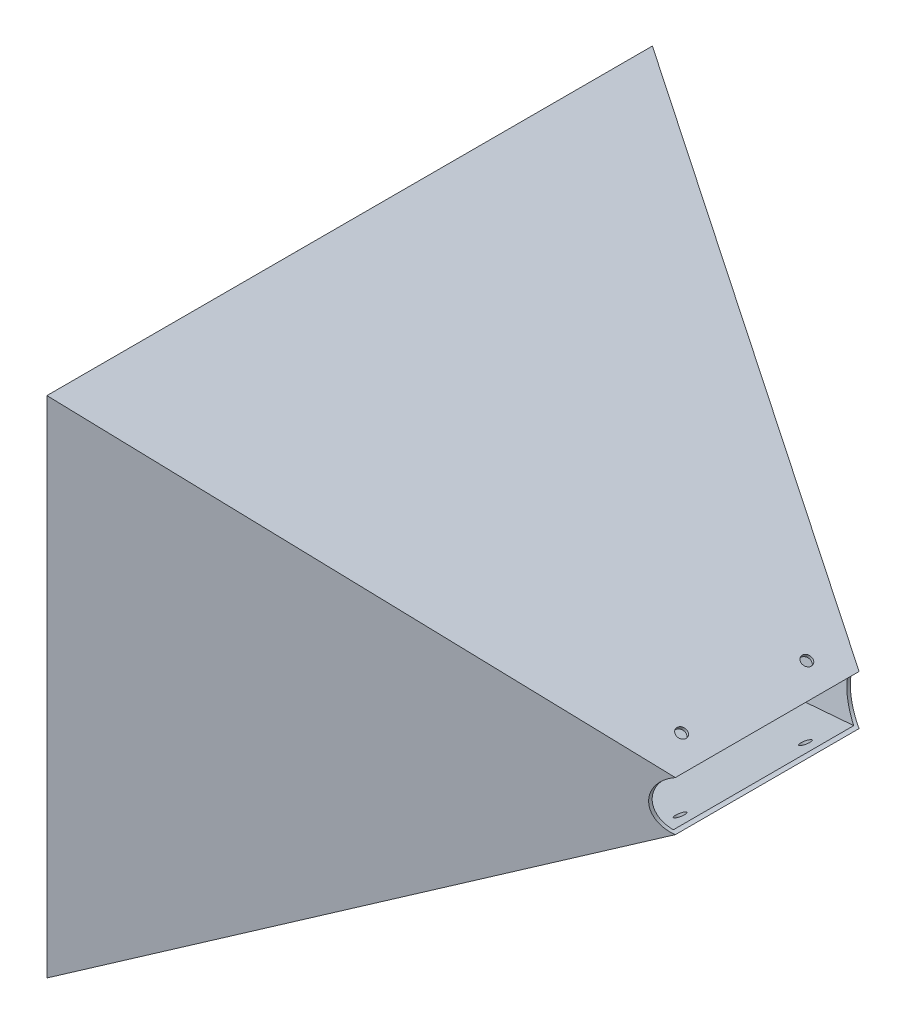
SolidWorks part; units mm, degrees
ref_plane "Front Plane" through (0, 0, 0) normal (0, 0, 1) x (1, 0, 0)
ref_plane "Top Plane" through (0, 0, 0) normal (0, 1, 0) x (1, 0, 0)
ref_plane "Right Plane" through (0, 0, 0) normal (1, 0, 0) x (0, 0, -1)
sketch "Sketch1" plane through (0, 0, 0) normal (0, 0, 1) x (1, 0, 0)
  line L0 (-4, -11.8427) -> (-204, -120.7957)
  line L1 (-4, -8.6168) -> (-204, -8.6168) construction
  line L2 (-204, 120.7957) -> (-4, 11.8427)
  line L3 (-4, -11.8427) -> (-4, -8.6168)
  line L4 (-4, 8.6168) -> (-4, 11.8427)
  line L5 (-204, -120.7957) -> (-204, 120.7957)
  arc A0 (-4, 8.6168) -> (-4, -8.6168) centre (0, 0) ccw
  dimension "D1" = 9.5
  dimension "D2" = 200
extrude "Boss-Extrude1" add sketch "Sketch1" along normal blind 290
ref_plane "Plane1" through (0, 0, 0) normal (0, -1, 0) x (-1, 0, 0)
sketch "Sketch2" plane through (0, 0, 0) normal (0, -1, 0) x (-1, 0, 0)
  line L0 (204, -145) -> (4, -145) construction
  line L1 (204, -290) -> (204, 0) construction
  line L2 (4, -290) -> (4, 0) construction
  line L3 (4, -145) -> (4, -189) construction
  line L4 (4, -189) -> (4, -101) construction
  line L5 (4, -145) -> (4, -101) construction
  line L6 (4, -189) -> (204, -290)
  line L7 (204, -290) -> (4, -290)
  line L8 (4, -290) -> (4, -189)
  line L9 (4, -101) -> (204, 0)
  line L10 (204, 0) -> (4, 0)
  line L11 (4, 0) -> (4, -101)
  dimension "D1" = 44
  dimension "D2" = 44
extrude "Cut-Extrude1" cut sketch "Sketch2" against normal blind 290 and the other way blind 290
shell "Shell3" thickness 1.5 removed face at (-6.75, 0, 145) removed face at (-204, 0, 145)
ref_plane "Plane2" through (4.0596, -7.4521, 0) normal (0.4784, -0.8782, 0) x (-0.8782, -0.4784, 0)
sketch "Sketch3" plane through (4.0596, -7.4521, 0) normal (0.4784, -0.8782, 0) x (-0.8782, -0.4784, 0)
  line L0 (9.178, -145) -> (236.9295, -145) construction
  line L1 (9.178, -189) -> (9.178, -101) construction
  line L2 (236.9295, -290) -> (236.9295, 0) construction
  line L3 (9.178, -145) -> (9.178, -175) construction
  line L4 (9.178, -175) -> (9.178, -115) construction
  line L5 (9.178, -145) -> (18.178, -145) construction
  line L6 (9.178, -175) -> (21.728, -175) construction
  line L7 (21.728, -175) -> (21.728, -115) construction
  line L8 (21.728, -115) -> (9.178, -115) construction
  circle A0 centre (21.728, -175) radius 2.5
  circle A1 centre (21.728, -115) radius 2.5
  dimension "D5" = 5
  dimension "D6" = 5
  dimension "D1" = 30
  dimension "D2" = 30
  dimension "D3" = 9
  dimension "D4" = 12.55
ref_plane "Plane3" through (4.0596, 7.4521, 0) normal (0.4784, 0.8782, 0) x (0.8782, -0.4784, 0)
sketch "Sketch4" plane through (4.0596, 7.4521, 0) normal (0.4784, 0.8782, 0) x (0.8782, -0.4784, 0)
  line L0 (-9.178, -101) -> (-9.178, -189) construction
  line L1 (-9.178, -189) -> (-9.178, -145) construction
  line L2 (-9.178, -145) -> (-236.9295, -145) construction
  line L3 (-236.9295, -290) -> (-236.9295, 0) construction
  line L4 (-9.178, -145) -> (-9.178, -115) construction
  line L5 (-9.178, -115) -> (-9.178, -175) construction
  line L6 (-9.178, -115) -> (-21.728, -115) construction
  line L7 (-21.728, -115) -> (-21.728, -175) construction
  line L8 (-21.728, -175) -> (-9.178, -175) construction
  circle A0 centre (-21.728, -115) radius 2.5
  circle A1 centre (-21.728, -175) radius 2.5
  dimension "D4" = 5
  dimension "D5" = 5
  dimension "D1" = 30
  dimension "D2" = 30
  dimension "D3" = 12.55
extrude "Cut-Extrude2" cut sketch "Sketch3" against normal blind 20
extrude "Cut-Extrude3" cut sketch "Sketch4" against normal blind 18 contours A1 | A0
ref_plane "Plane4" through (0, 0, 145) normal (0, 0, 1) x (1, 0, 0)
sketch "Sketch6" plane through (0, 0, 145) normal (0, 0, 1) x (1, 0, 0)
  line L0 (-4, 11.8427) -> (-4, -11.8427)
  arc A0 (-4, 11.8427) -> (-4, -11.8427) centre (0, 0) ccw
  dimension "D1" = 12.5
extrude "Cut-Extrude4" cut sketch "Sketch6" against normal blind 128 and the other way blind 119
